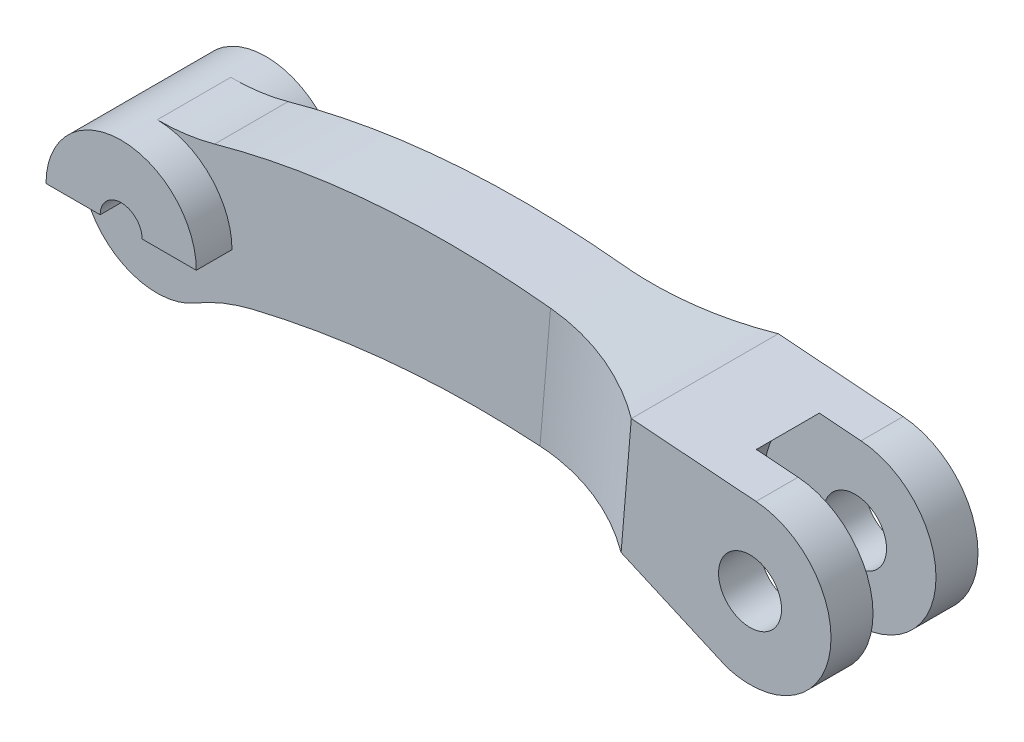
SolidWorks part; units mm, degrees
ref_plane "Спереди" through (0, 0, 0) normal (0, 0, 1) x (1, 0, 0)
ref_plane "Сверху" through (0, 0, 0) normal (0, 1, 0) x (1, 0, 0)
ref_plane "Справа" through (0, 0, 0) normal (1, 0, 0) x (0, 0, -1)
sketch "Sketch1" plane through (0, 0, 0) normal (0, 0, 1) x (1, 0, 0)
  line L2 (0, 0) -> (1, 0) construction
  line L3 (2.5683, -2.4924) -> (15.4492, 1.1857) construction
  line L4 (15.4492, 1.1857) -> (28.4491, -2.568) construction
  line L5 (1.0378, 3.4251) -> (13.95, 7.6491) construction
  line L6 (13.95, 7.6491) -> (29.5304, 2.963) construction
  circle A0 centre (0, 0) radius 1
  arc A2 (28.4491, -2.568) -> (29.5304, 2.963) centre (30, 0) ccw
  circle A3 centre (30, 0) radius 1.5
  arc A4 (1.0378, 3.4251) -> (2.5683, -2.4924) centre (0, 0) ccw
  spline S0 degree 2 poles (2.5683, -2.4924) (15.4492, 1.1857) (28.4491, -2.568) knots 0 0 0 1 1 1
  spline S1 degree 2 poles (1.0378, 3.4251) (13.95, 7.6491) (29.5304, 2.963) knots 0 0 0 1 1 1
  dimension "D4" = 2
  dimension "D6" = 3
  dimension "D7" = 6
  dimension "D2" = 30
extrude "Boss-Extrude1" add sketch "Sketch1" along normal mid plane 3.5
fillet "Fillet1" radius 3 1 edges at (29.5304, 2.963, 0)
sketch "Sketch2" plane through (0, 0, 0) normal (0, 0, 1) x (1, 0, 0)
  line L0 (30.2881, 3.8462) -> (24.346, 4.2913)
  line L1 (24.346, 4.2913) -> (23.8601, -1.4737)
  line L2 (23.8601, -1.4737) -> (28.9253, -3.7042)
  circle A0 centre (30, 0) radius 1.5
  circle A1 centre (30, 0) radius 1.5 construction
  arc A2 (28.9253, -3.7042) -> (30.2881, 3.8462) centre (30, 0) ccw
  parabola Q0 (29.0064, 3.1183) -> (1.0378, 3.4251) focus (7.6812, -15.2738) apex (1.9924, 3.7242) construction
  parabola Q1 (2.5683, -2.4924) -> (28.4491, -2.568) focus (14.9866, -23.1959) apex (14.626, -0.6778) construction
extrude "Boss-Extrude2" add sketch "Sketch2" along normal mid plane 7
sketch "Sketch3" plane through (0, 0, 0) normal (0, 0, 1) x (1, 0, 0)
  circle A0 centre (30, 0) radius 4.342
extrude "Cut-Extrude1" cut sketch "Sketch3" against normal mid plane 3
fillet "Fillet2" radius 10 2 edges at (24.103, 1.4088, -1.75) (24.103, 1.4088, 1.75)
fillet "Fillet3" radius 10 2 edges at (1.0378, 3.4251, 0) (2.5683, -2.4924, 0)
sketch "Sketch4" plane through (0, 0, 1.75) normal (0, 0, 1) x (1, 0, 0)
  line L0 (-1, 0) -> (-3.5789, 0)
  line L1 (1, 0) -> (3.5789, 0)
  circle A0 centre (0, 0) radius 1 construction
  arc A1 (0.02, 3.5788) -> (1.822, -3.0804) centre (0, 0) ccw construction
  arc A2 (1, 0) -> (-1, 0) centre (0, 0) ccw
  arc A3 (3.5789, 0) -> (-3.5789, 0) centre (0, 0) ccw
extrude "Boss-Extrude3" add sketch "Sketch4" along normal blind 1.7
extrude "Boss-Extrude4" add sketch "Sketch4<2>" against normal blind 1.7 from surface starting at face at (1, 0, -1.75)
sketch "Sketch4<2>" plane through (0, 0, 1.75) normal (0, 0, 1) x (1, 0, 0) same geometry as "Sketch4"
